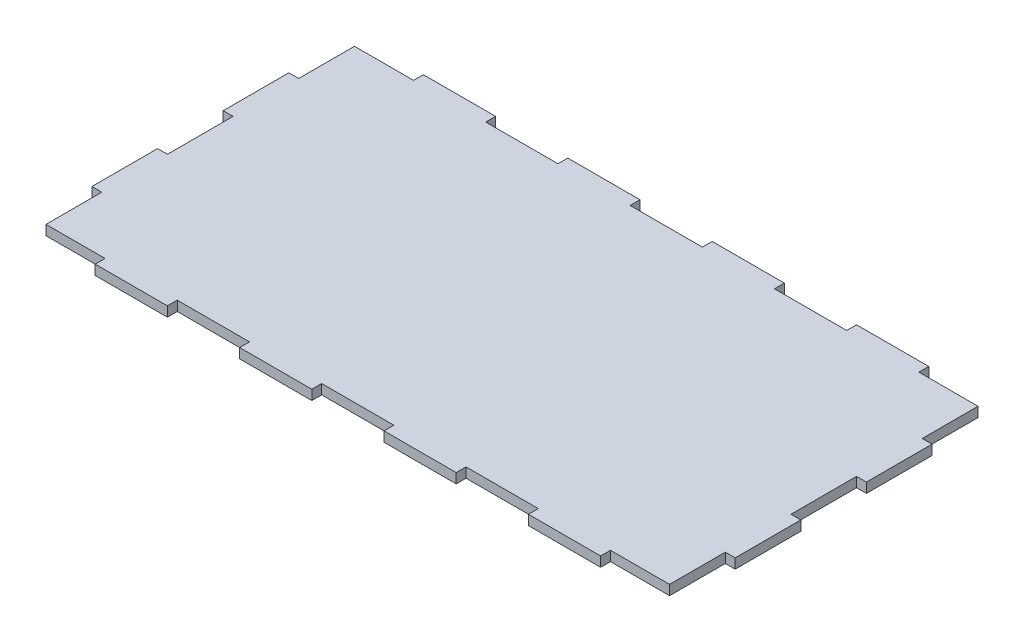
SolidWorks part; units mm, degrees
ref_plane "Front Plane" through (0, 0, 0) normal (0, 0, 1) x (1, 0, 0)
ref_plane "Top Plane" through (0, 0, 0) normal (0, 1, 0) x (1, 0, 0)
ref_plane "Right Plane" through (0, 0, 0) normal (1, 0, 0) x (0, 0, -1)
sketch "Sketch1" plane through (0, 0, 0) normal (0, 1, 0) x (1, 0, 0)
  line L0 (-77, -50) -> (-77, -47)
  line L1 (-98, -50) -> (98, -50)
  line L2 (-98, -50) -> (-98, 50)
  line L3 (-98, 50) -> (98, 50)
  line L4 (98, -50) -> (98, 50)
  line L5 (-98, -50) -> (98, 50) construction
  line L6 (-98, 50) -> (98, -50) construction
  line L7 (-98, -30) -> (-95, -30)
  line L8 (-55, -50) -> (-55, -47)
  line L9 (-55, -47) -> (-33, -47)
  line L10 (-33, -47) -> (-33, -50)
  line L11 (-33, -50) -> (-11, -50)
  line L12 (-11, -50) -> (-11, -47)
  line L13 (-11, -47) -> (11, -47)
  line L14 (11, -47) -> (11, -50)
  line L15 (11, -50) -> (33, -50)
  line L16 (33, -50) -> (33, -47)
  line L17 (33, -47) -> (55, -47)
  line L18 (55, -47) -> (55, -50)
  line L19 (55, -50) -> (77, -50)
  line L20 (77, -50) -> (77, -47)
  line L21 (77, -47) -> (95, -47)
  line L22 (-77, 47) -> (-95, 47)
  line L23 (-77, 47) -> (-77, 50)
  line L24 (-77, 50) -> (-55, 50)
  line L25 (-55, 50) -> (-55, 47)
  line L26 (-55, 47) -> (-33, 47)
  line L27 (-33, 47) -> (-33, 50)
  line L28 (-33, 50) -> (-11, 50)
  line L29 (-11, 50) -> (-11, 47)
  line L30 (-11, 47) -> (11, 47)
  line L31 (11, 47) -> (11, 50)
  line L32 (11, 50) -> (33, 50)
  line L33 (33, 50) -> (33, 47)
  line L34 (33, 47) -> (55, 47)
  line L35 (55, 47) -> (55, 50)
  line L36 (55, 50) -> (77, 50)
  line L37 (77, 50) -> (77, 47)
  line L38 (77, 47) -> (95, 47)
  line L39 (-95, 47) -> (-95, 30)
  line L40 (-95, 30) -> (-98, 30)
  line L41 (-98, 30) -> (-98, 10)
  line L42 (-98, 10) -> (-95, 10)
  line L43 (-95, 10) -> (-95, -10)
  line L44 (-95, -10) -> (-98, -10)
  line L45 (98, -10) -> (95, -10)
  line L46 (-95, -30) -> (-95, -47)
  line L47 (-95, -47) -> (-77, -47)
  line L48 (95, -10) -> (95, 10)
  line L49 (95, 10) -> (98, 10)
  line L50 (98, 10) -> (98, 30)
  line L51 (98, 30) -> (95, 30)
  line L52 (95, 30) -> (95, 47)
  line L53 (98, -30) -> (95, -30)
  line L54 (95, -30) -> (95, -47)
  line L55 (95, 47) -> (95.0857, 46.8787)
  point P0 (0, 0)
  dimension "D1" = 100
  dimension "D2" = 196
  dimension "D3" = 3
  dimension "D4" = 22
  dimension "D5" = 22
  dimension "D6" = 22
  dimension "D7" = 22
  dimension "D8" = 22
  dimension "D9" = 22
  dimension "D10" = 22
  dimension "D11" = 3
  dimension "D12" = 3
  dimension "D13" = 3
  dimension "D14" = 3
  dimension "D15" = 3
  dimension "D16" = 3
  dimension "D17" = 3
  dimension "D18" = 20
  dimension "D19" = 3
  dimension "D20" = 20
  dimension "D21" = 3
  dimension "D22" = 20
  dimension "D23" = 20
  dimension "D24" = 3
  dimension "D25" = 3
  dimension "D26" = 3
  dimension "D27" = 20
  dimension "D28" = 20
  dimension "D29" = 20
  dimension "D30" = 3
  dimension "D31" = 20
extrude "Boss-Extrude2" add sketch "Sketch1" along normal blind 3 contours L20 L4 L3 L2 L0 L1 L8 L9 L10 L12 L13 L14 L16 L17 L18 region at (0, 0, 0)
